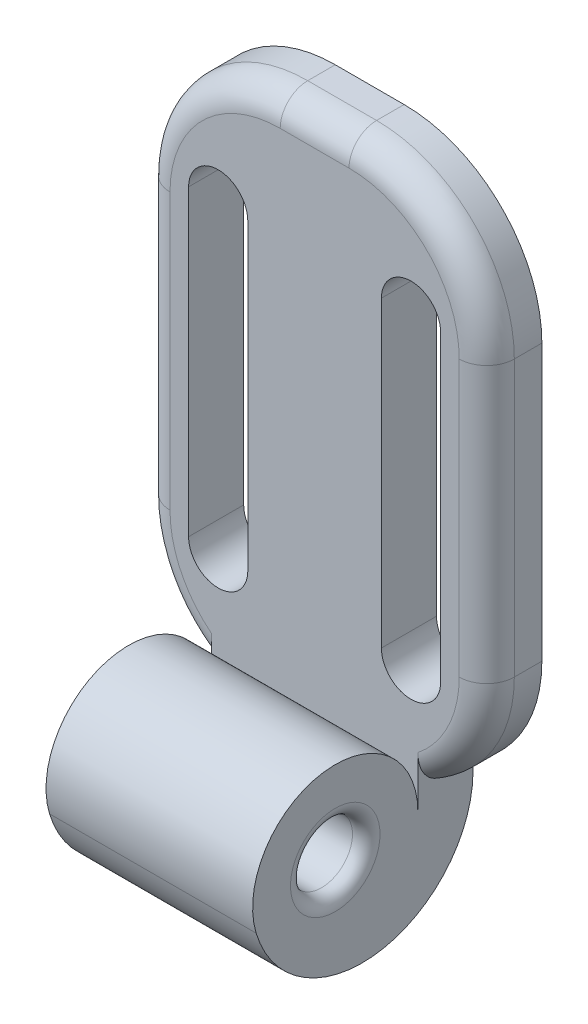
SolidWorks part; units mm, degrees
ref_plane "Front Plane" through (0, 0, 0) normal (0, 0, 1) x (1, 0, 0)
ref_plane "Top Plane" through (0, 0, 0) normal (0, 1, 0) x (1, 0, 0)
ref_plane "Right Plane" through (0, 0, 0) normal (1, 0, 0) x (0, 0, -1)
sketch "Sketch1" plane through (0, 0, 0) normal (0, 0, 1) x (1, 0, 0)
  line L0 (0, 0) -> (-7, 0) construction
  line L1 (12.5, -20) -> (-12.5, -20)
  line L2 (12.5, -20) -> (12.5, 20)
  line L3 (12.5, 20) -> (-12.5, 20)
  line L4 (-12.5, -20) -> (-12.5, 20)
  line L5 (12.5, -20) -> (-12.5, 20) construction
  line L6 (12.5, 20) -> (-12.5, -20) construction
  line L7 (-7, -11) -> (-7, 11) construction
  line L8 (-9.15, -11) -> (-9.15, 11)
  line L9 (-4.85, -11) -> (-4.85, 11)
  line L10 (0, -55) -> (0, 55) construction
  line L11 (7, -11) -> (7, 11) construction
  line L12 (9.15, -11) -> (9.15, 11)
  line L13 (4.85, -11) -> (4.85, 11)
  arc A0 (-9.15, -11) -> (-4.85, -11) centre (-7, -11) ccw
  arc A1 (-4.85, 11) -> (-9.15, 11) centre (-7, 11) ccw
  arc A2 (9.15, -11) -> (4.85, -11) centre (7, -11) cw
  arc A3 (4.85, 11) -> (9.15, 11) centre (7, 11) cw
  point P0 (0, 0)
  point P10 (-7, 0)
  point P15 (-7, 0)
  point P20 (7, 0)
  dimension "D4" = 2.15
  dimension "D1" = 7
  dimension "D2" = 25
  dimension "D3" = 22
  dimension "D5" = 40
extrude "Boss-Extrude1" add sketch "Sketch1" along normal mid plane 4
sketch "Sketch2" plane through (0, 0, 0) normal (1, 0, 0) x (0, 0, -1)
  line L0 (2, -20) -> (-2, -20)
  line L1 (2, -20) -> (2, 20) construction
  arc A0 (-2, -20) -> (-13.7452, -21.7298) centre (-8, -20) ccw
  circle A1 centre (-8, -20) radius 2.25
  arc A2 (-13.7452, -21.7298) -> (1.9784, -20) centre (-6.0434, -19.4109) ccw
  dimension "D1" = 12
  dimension "D2" = 4.5
  dimension "D3" = 10
extrude "Boss-Extrude2" add sketch "Sketch2" along normal mid plane 15 contours A0 A2 L0 A1 region at (0, -27.1984, 5.1867)
sketch "Sketch3" plane through (7.5, 0, 0) normal (1, 0, 0) x (0, 0, -1)
  circle A0 centre (-8, -20) radius 2.25 construction
  circle A1 centre (-8, -20) radius 2.25
fillet "Fillet1" radius 10 4 edges at (-12.5, 20, 0) (12.5, 20, 0) (-12.5, -20, 0) (12.5, -20, 0)
fillet "Fillet3" radius 2 7 edges at (11.1603, -15, 2) (12.5, 0, 2) (9.5711, 17.0711, 2) (-11.1603, -15, 2) (-12.5, 0, 2) (-9.5711, 17.0711, 2) (0, 20, 2)
fillet "Fillet5" radius 1 2 edges at (-7.5, -20, 5.75) (7.5, -20, 5.75)
